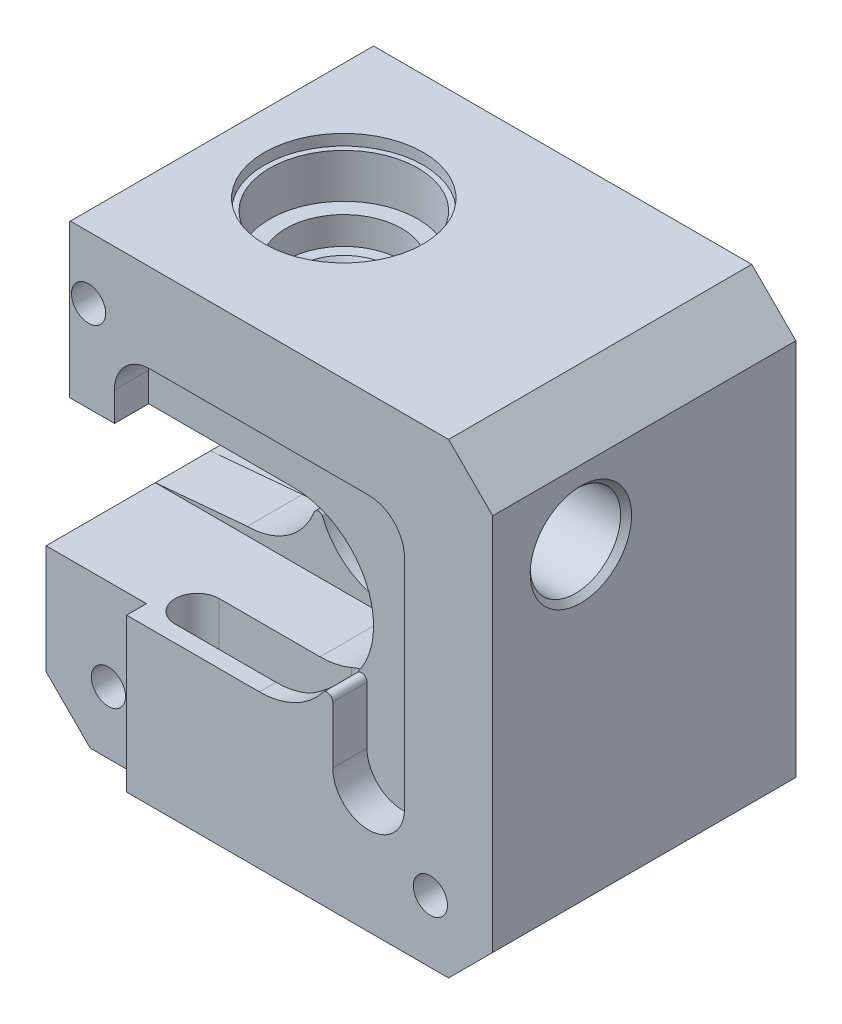
SolidWorks part; units mm, degrees
material "aluminio"
ref_plane "Alzado" through (0, 0, 0) normal (0, 0, 1) x (1, 0, 0)
ref_plane "Planta" through (0, 0, 0) normal (0, 1, 0) x (1, 0, 0)
ref_plane "Vista lateral" through (0, 0, 0) normal (1, 0, 0) x (0, 0, -1)
sketch "Croquis1" plane through (0, 0, 0) normal (0, 0, 1) x (1, 0, 0)
  line L1 (0, 0) -> (42.3, 0)
  line L2 (0, 0) -> (0, 42.3)
  line L3 (0, 42.3) -> (42.3, 42.3)
  line L4 (42.3, 0) -> (42.3, 42.3)
  dimension "D1" = 42.3
  dimension "D2" = 42.3
extrude "Saliente-Extruir1" add sketch "Croquis1" along normal blind 28
chamfer "Chaflán1" distance 4 angle 45 4 edges at (42.3, 0, 14) (0, 0, 14) (42.3, 42.3, 14) (0, 42.3, 14)
sketch "Croquis5" plane through (0, 0, 28) normal (0, 0, 1) x (1, 0, 0)
  line L0 (0, 38.3) -> (0, 4) construction
  line L1 (0, 28.4) -> (28.4, 28.4)
  line L2 (0, 28.4) -> (0, 13.9)
  line L3 (0, 13.9) -> (28.4, 13.9)
  line L4 (28.4, 28.4) -> (28.4, 13.9)
  line L5 (42.3, 21.15) -> (28.4, 21.15) construction
  line L6 (42.3, 4) -> (42.3, 38.3) construction
  dimension "D1" = 14.5
  dimension "D2" = 28.4
extrude "Cortar-Extruir4" cut sketch "Croquis5" against normal up to surface (28 mm away) up to face at (21.15, 21.15, 0)
sketch "Croquis6" plane through (0, 0, 0) normal (-1, 0, 0) x (0, 0, 1)
  line L0 (0, 28.4) -> (28, 28.4) construction
  line L1 (11.7, 28.4) -> (16.7, 28.4)
  line L2 (11.7, 28.4) -> (11.7, 13.9)
  line L3 (11.7, 13.9) -> (16.7, 13.9)
  line L4 (16.7, 28.4) -> (16.7, 13.9)
  line L6 (0, 13.9) -> (28, 13.9) construction
  line L7 (0, 13.9) -> (0, 28.4) construction
  dimension "D1" = 5
  dimension "D2" = 11.7
extrude "Saliente-Extruir2" add sketch "Croquis6" against normal up to surface (28.4 mm away) up to face at (28.4, 21.15, 14)
sketch "Croquis7" plane through (0, 0, 16.7) normal (0, 0, 1) x (1, 0, 0)
  line L0 (0, 21.15) -> (8.35, 21.15) construction
  line L1 (0, 13.9) -> (0, 28.4) construction
  line L2 (0, 27.65) -> (8.35, 27.65)
  line L3 (0, 14.65) -> (8.35, 14.65)
  line L4 (0, 13.9) -> (0, 4) construction
  line L5 (14.7726, 22.15) -> (14.8286, 22.15)
  line L6 (21.15, 21.15) -> (42.3, 21.15) construction
  line L7 (42.3, 4) -> (42.3, 38.3) construction
  line L11 (14.7726, 20.15) -> (14.8286, 20.15)
  arc A0 (14.8286, 20.15) -> (14.8286, 22.15) centre (21.15, 21.15) ccw
  arc A1 (0, 27.65) -> (0, 14.65) centre (0, 21.15) ccw
  arc A2 (8.35, 14.65) -> (14.7726, 20.15) centre (8.35, 21.15) ccw
  arc A3 (14.7726, 22.15) -> (8.35, 27.65) centre (8.35, 21.15) ccw
  dimension "D1" = 6.5
  dimension "D2" = 12.8
  dimension "D6" = 6.5
  dimension "D3" = 12.8
  dimension "D4" = 21.15
  dimension "D5" = 2
extrude "Cortar-Extruir5" cut sketch "Croquis7" against normal up to next
sketch "Croquis3" plane through (0, 42.3, 0) normal (0, 1, 0) x (1, 0, 0)
  line L0 (4, -14.2) -> (14.6, -14.2) construction
  line L2 (0, -28) -> (0, 0) construction
  line L3 (38.3, 0) -> (4, 0) construction
  circle A0 centre (14.6, -14.2) radius 1.9
  dimension "D1" = 3.8
  dimension "D2" = 14.6
  dimension "D3" = 14.2
extrude "Cortar-Extruir2" cut sketch "Croquis3" against normal through all
sketch "Croquis8" plane through (0, 0, 11.7) normal (0, 0, -1) x (-1, 0, 0)
  line L0 (-8.35, 14.65) -> (0, 13.9)
  line L1 (0, 13.9) -> (0, 14.65)
  line L2 (0, 14.65) -> (-8.35, 14.65)
  line L3 (0, 28.4) -> (-8.35, 27.65)
  line L4 (-8.35, 27.65) -> (0, 27.65)
  line L5 (0, 27.65) -> (0, 28.4)
extrude "Cortar-Extruir6" cut sketch "Croquis8" against normal blind 20
sketch "Croquis9" plane through (0, 0, 0) normal (0, 0, -1) x (-1, 0, 0)
  line L0 (-36.65, 36.65) -> (-5.65, 36.65) construction
  line L1 (-5.65, 36.65) -> (-5.65, 5.65) construction
  line L2 (-5.65, 5.65) -> (-36.65, 5.65) construction
  line L3 (-36.65, 5.65) -> (-36.65, 36.65) construction
  line L4 (-21.15, 36.65) -> (-21.15, 42.3) construction
  line L5 (-38.3, 42.3) -> (-4, 42.3) construction
  line L6 (-42.3, 21.15) -> (-36.65, 21.15) construction
  line L7 (-42.3, 4) -> (-42.3, 38.3) construction
  circle A0 centre (-36.65, 36.65) radius 1.55 construction
  circle A1 centre (-5.65, 36.65) radius 1.55
  circle A2 centre (-5.65, 5.65) radius 1.55
  circle A3 centre (-36.65, 5.65) radius 1.55
  dimension "D2" = 3.1
  dimension "D1" = 31
extrude "Cortar-Extruir7" cut sketch "Croquis9" against normal up to surface (28 mm away) up to face at (18.8333, 21.15, 28)
sketch "Croquis10" plane through (0, 42.3, 0) normal (0, 1, 0) x (1, 0, 0)
  circle A0 centre (14.6, -14.2) radius 6.725
  dimension "D1" = 13.45
extrude "Cortar-Extruir8" cut sketch "Croquis10" against normal blind 5
sketch "Croquis11" plane through (0, 37.3, 0) normal (0, 1, 0) x (1, 0, 0)
  circle A0 centre (14.6, -14.2) radius 5.25
  dimension "D1" = 10.5
extrude "Cortar-Extruir9" cut sketch "Croquis11" against normal blind 2.5
sketch "Croquis12" plane through (0, 34.8, 0) normal (0, 1, 0) x (1, 0, 0)
  circle A0 centre (14.6, -14.2) radius 3.25
  dimension "D1" = 6.5
extrude "Cortar-Extruir10" cut sketch "Croquis12" against normal blind 6
sketch "Croquis15" plane through (0, 42.3, 0) normal (0, 1, 0) x (1, 0, 0)
  circle A0 centre (14.6, -14.2) radius 7.2
  dimension "D1" = 14.4
extrude "Cortar-Extruir13" cut sketch "Croquis15" against normal blind 1
chamfer "Chaflán2" distance 1 angle 60 1 edges at (14.6, 34.8, 17.45) first distance on face at (14.6, 34.8, 17.45)
ref_plane "Plano1" through (0, 21.15, 0) normal (0, 1, 0) x (1, 0, 0)
mirror "Simetría1" about plane through (0, 21.15, 0) normal (0, 1, 0) of "Cortar-Extruir13", "Cortar-Extruir8", "Cortar-Extruir9", "Cortar-Extruir10"
chamfer "Chaflán4" distance 1 angle 60 1 edges at (14.6, 7.5, 17.45) first distance on face at (14.6, 7.5, 17.45)
chamfer "Chaflán5" distance 0.7 angle 60 1 edges at (14.6, 13.5, 12.3) first distance on face at (14.6, 13.5, 17.45)
chamfer "Chaflán6" [suppressed] distance 0.5 angle 60
ref_plane "Plano2" through (0, 0, 14) normal (0, 0, 1) x (1, 0, 0)
sketch "Croquis18" plane through (0, 42.3, 0) normal (0, 1, 0) x (1, 0, 0)
  line L0 (12, -24.5) -> (24, -24.5) construction
  line L1 (12, -22.5) -> (24, -22.5) construction
  line L2 (12, -26.5) -> (24, -26.5) construction
  line L3 (38.3, -28) -> (4, -28) construction
  line L4 (4, -14) -> (38.3, -14) construction
  line L5 (0, -28) -> (0, 0) construction
  line L6 (4, 0) -> (4, -28) construction
  line L7 (38.3, -28) -> (38.3, 0) construction
  line L8 (12, -3.5) -> (24, -3.5) construction
  line L9 (12, -5.5) -> (24, -5.5)
  line L10 (12, -1.5) -> (24, -1.5)
  arc A0 (12, -22.5) -> (12, -26.5) centre (12, -24.5) ccw construction
  arc A1 (24, -26.5) -> (24, -22.5) centre (24, -24.5) ccw construction
  arc A2 (12, -5.5) -> (12, -1.5) centre (12, -3.5) cw
  arc A3 (24, -1.5) -> (24, -5.5) centre (24, -3.5) cw
  point P2 (18, -24.5)
  point P19 (18, -3.5)
  dimension "D1" = 2
  dimension "D2" = 12
  dimension "D3" = 1.5
  dimension "D4" = 12
extrude "Cortar-Extruir17" cut sketch "Croquis18" against normal up to surface (13.9 mm away) from surface at -28.4 up to face at (14.6, 0, 21.4) starting at face at (14.2, 13.9, 5.85)
sketch "Croquis21" plane through (0, 0, 16.7) normal (0, 0, 1) x (1, 0, 0)
  line L1 (14.5014, 23.25) -> (15.1043, 23.25)
  line L2 (14.5014, 23.25) -> (14.5014, 19.05)
  line L3 (14.5014, 19.05) -> (15.1043, 19.05)
  line L4 (15.1043, 23.25) -> (15.1043, 19.05)
  arc A0 (8.35, 14.65) -> (14.7726, 20.15) centre (8.35, 21.15) ccw construction
  circle A1 centre (21.15, 21.15) radius 6.4 construction
  dimension "D1" = 4.2
  dimension "D2" = 0.6029
extrude "Cortar-Extruir19" cut sketch "Croquis21" against normal through all
sketch "Croquis22" plane through (0, 0, 0) normal (-1, 0, 0) x (0, 0, 1)
  line L2 (8, 32.3) -> (8, 31.8) construction
  line L3 (9.55, 32.3) -> (9.55, 31.8) construction
  line L4 (6.45, 32.3) -> (6.45, 31.8) construction
  line L5 (0, 38.3) -> (0, 28.4) construction
  line L6 (0, 42.3) -> (28, 42.3) construction
  arc A0 (9.55, 32.3) -> (6.45, 32.3) centre (8, 32.3) ccw construction
  arc A1 (6.45, 31.8) -> (9.55, 31.8) centre (8, 31.8) ccw construction
  circle A2 centre (8, 32.05) radius 2.5
  point P2 (8, 32.05)
  dimension "D1" = 1.55
  dimension "D5" = 5
  dimension "D2" = 0.5
  dimension "D3" = 8
  dimension "D4" = 10
extrude "Cortar-Extruir20" cut sketch "Croquis22" against normal through all
fillet "Redondeo1" radius 0.4 8 edges at (14.5014, 19.05, 12.0013) (15.1043, 19.05, 12.0341) (15.1043, 19.05, 16.3659) (14.5014, 19.05, 16.3987) (15.1043, 23.25, 16.3659) (15.1043, 23.25, 12.0341) (14.5014, 23.25, 12.0013) (14.5014, 23.25, 16.3987)
sketch "Croquis25" plane through (0, 42.3, 0) normal (0, 1, 0) x (1, 0, 0)
  line L0 (42.3, 0) -> (42.3, -28) construction
  line L1 (0, -28) -> (42.3, -28)
  line L2 (0, -28) -> (0, -27.5)
  line L3 (0, -27.5) -> (42.3, -27.5)
  line L4 (42.3, -28) -> (42.3, -27.5)
  dimension "D1" = 0.5
extrude "Cortar-Extruir23" cut sketch "Croquis25" against normal through all
sketch "Croquis34" plane through (0, 0, 0) normal (-1, 0, 0) x (0, 0, 1)
  line L0 (27.5, 0) -> (0, 0) construction
  line L1 (0, 13.9) -> (1.8, 13.9)
  line L2 (0, 13.9) -> (0, 0)
  line L3 (0, 0) -> (1.8, 0)
  line L4 (1.8, 13.9) -> (1.8, 0)
  line L5 (16.7, 13.9) -> (27.5, 13.9) construction
  line L6 (19.8, 13.9) -> (24.3, 13.9)
  line L7 (19.8, 13.9) -> (19.8, 0)
  line L8 (19.8, 0) -> (24.3, 0)
  line L9 (24.3, 13.9) -> (24.3, 0)
  dimension "D1" = 1.8
  dimension "D2" = 19.8
  dimension "D3" = 4.5
extrude "Cortar-Extruir28" cut sketch "Croquis34" against normal blind 9.1
fillet "Redondeo6" radius 7.25 4 edges at (28.4, 28.4, 5.85) (28.4, 13.9, 5.85) (28.4, 13.9, 22.1) (28.4, 28.4, 22.1)
sketch "Croquis35" plane through (0, 0, 0) normal (-1, 0, 0) x (0, 0, 1)
  line L0 (0, 28.4) -> (0, 21.15) construction
  line L2 (24.7, 27.4) -> (24.7, 29.15)
  line L3 (0, 27.4) -> (0, 42.3)
  line L4 (0, 42.3) -> (12.7, 42.3)
  line L5 (0, 42.3) -> (27.5, 42.3) construction
  line L6 (12.7, 42.3) -> (12.7, 37.65)
  line L7 (12.7, 37.65) -> (16.2, 37.65)
  line L8 (27.5, 28.4) -> (27.5, 38.3) construction
  line L9 (0, 27.4) -> (24.7, 27.4)
  line L10 (0, 28.4) -> (11.7, 28.4) construction
  arc A0 (16.2, 37.65) -> (24.7, 29.15) centre (16.2, 29.15) cw
  dimension "D1" = 8.5
  dimension "D2" = 2.8
  dimension "D3" = 4.65
  dimension "D4" = 12.7
  dimension "D5" = 1
extrude "Cortar-Extruir29" cut sketch "Croquis35" against normal blind 3.9
fillet "Redondeo7" radius 2 1 edges at (1.95, 37.65, 12.7)
sketch "Croquis24" plane through (42.3, 0, 0) normal (1, 0, 0) x (0, 0, -1)
  circle A0 centre (-8, 32.05) radius 4.1
  dimension "D1" = 8.2
extrude "Cortar-Extruir22" cut sketch "Croquis24" against normal blind 17
chamfer "Chaflán7" distance 0.5 angle 45 1 edges at (42.3, 36.15, 8)
sketch "Croquis36" plane through (0, 0, 0) normal (0, 0, -1) x (-1, 0, 0)
  line L0 (-34.2995, 31.0495) -> (-34.2995, 11.2505)
  line L1 (-31.0495, 34.2995) -> (-11.2505, 34.2995)
  line L2 (-24, 0) -> (-24, 14.4837) construction
  line L3 (-27.7995, 11.2505) -> (-27.7995, 27.7995)
  line L4 (-27.7995, 27.7995) -> (-11.2505, 27.7995)
  line L5 (-8.0005, 31.0495) -> (-8.0005, 28.4)
  line L6 (-21.15, 28.4) -> (-3.9, 28.4) construction
  line L10 (-3.9, 28.4) -> (-3.9, 42.2)
  line L11 (-3.9, 42.2) -> (-4, 42.3)
  line L12 (-4, 42.3) -> (-38.3, 42.3)
  line L13 (-38.3, 42.3) -> (-42.3, 38.3)
  line L14 (-42.3, 38.3) -> (-42.3, 4)
  line L15 (-42.3, 4) -> (-38.3, 0)
  line L16 (-38.3, 0) -> (-9.1, 0)
  line L17 (-9.1, 0) -> (-9.1, 13.9)
  line L18 (-9.1, 13.9) -> (-21.15, 13.9)
  line L19 (-21.15, 28.4) -> (-3.9, 28.4)
  line L20 (-3.9, 28.4) -> (-3.9, 42.2)
  line L21 (-3.9, 42.2) -> (-4, 42.3)
  line L22 (-4, 42.3) -> (-38.3, 42.3)
  line L23 (-38.3, 42.3) -> (-42.3, 38.3)
  line L24 (-42.3, 38.3) -> (-42.3, 4)
  line L25 (-42.3, 4) -> (-38.3, 0)
  line L26 (-38.3, 0) -> (-9.1, 0)
  line L27 (-9.1, 0) -> (-9.1, 13.9)
  line L28 (-9.1, 13.9) -> (-24, 13.9)
  circle A0 centre (-31.0495, 11.2505) radius 2.75 construction
  circle A1 centre (-11.2505, 31.0495) radius 2.75 construction
  arc A2 (-28.4, 21.15) -> (-21.15, 13.9) centre (-21.15, 21.15) ccw
  arc A3 (-21.15, 28.4) -> (-28.4, 21.15) centre (-21.15, 21.15) ccw
  arc A4 (-28.4, 21.15) -> (-21.15, 13.9) centre (-21.15, 21.15) ccw
  arc A5 (-21.15, 28.4) -> (-28.4, 21.15) centre (-21.15, 21.15) ccw
  circle A6 centre (-31.0495, 31.0495) radius 2.75 construction
  circle A7 centre (-31.0495, 11.2505) radius 2.75 construction
  circle A8 centre (-11.2505, 31.0495) radius 2.75 construction
  circle A9 centre (-31.0495, 31.0495) radius 2.75 construction
  circle A10 centre (-11.2505, 31.0495) radius 3.25
  circle A11 centre (-31.0495, 31.0495) radius 3.25
  circle A12 centre (-31.0495, 11.2505) radius 3.25
  dimension "D2" = 6.5
  dimension "D1" = 0
extrude "Cortar-Extruir30" cut sketch "Croquis36" against normal blind 3.1
fillet "Redondeo10" radius 0.5 1 edges at (27.7995, 18.2609, 1.55) type face fillet first side face at (24.9348, 16.1842, 4.3388) second side face at (27.7995, 14.7557, 1.55)
ref_plane "Plano3" through (0, 0, 13.75) normal (0, 0, -1) x (-1, 0, 0)
mirror "Simetría2" about plane through (0, 0, 13.75) normal (0, 0, -1) of bodies 141
delete or keep bodies "Sólido-Eliminar/Conservar 1" type delete bodies bodies 141
